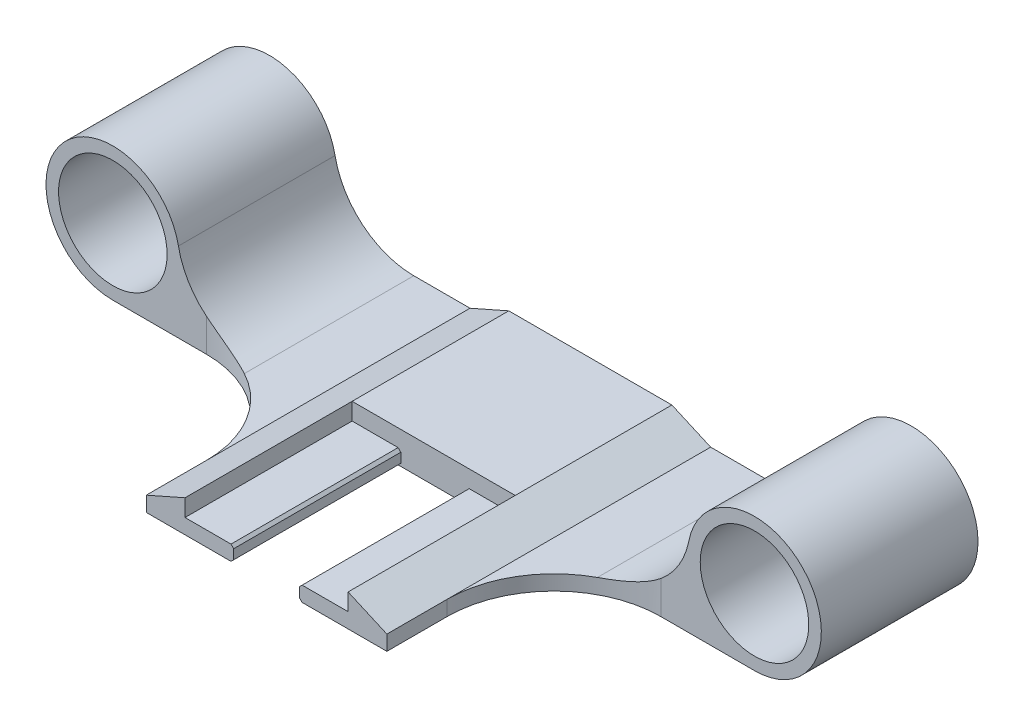
SolidWorks part; units mm, degrees
ref_plane "Front Plane" through (0, 0, 0) normal (0, 0, 1) x (1, 0, 0)
ref_plane "Top Plane" through (0, 0, 0) normal (0, 1, 0) x (1, 0, 0)
ref_plane "Right Plane" through (0, 0, 0) normal (1, 0, 0) x (0, 0, -1)
sketch "Sketch1" plane through (0, 0, 0) normal (0, 0, 1) x (1, 0, 0)
  line L1 (-22.5, -1.4) -> (-6.15, -1.4)
  line L2 (-22.5, -1.4) -> (-22.5, 1.4)
  line L3 (-15.25, 1.4) -> (-6.15, 1.4)
  line L4 (22.5, -1.4) -> (22.5, 1.4)
  line L5 (-22.5, -1.4) -> (22.5, 1.4) construction
  line L6 (-22.5, 1.4) -> (22.5, -1.4) construction
  line L8 (-6.15, -1.4) -> (-6.15, 1.4)
  line L10 (6.15, -1.4) -> (6.15, 1.4)
  line L11 (-6.15, -1.4) -> (6.15, 1.4) construction
  line L12 (-6.15, 1.4) -> (6.15, -1.4) construction
  line L13 (15.25, 1.4) -> (15.25, 4.6)
  line L14 (15.25, 4.6) -> (22.5, 1.4)
  line L15 (6.15, -1.4) -> (22.5, -1.4)
  line L16 (-15.25, 1.4) -> (-15.25, 4.6)
  line L17 (-15.25, 4.6) -> (-22.5, 1.4)
  line L19 (6.15, 1.4) -> (15.25, 1.4)
  point P0 (0, 0)
  point P6 (0, 0)
  point P11 (0, 0)
  point P14 (0, 1.4)
  point P16 (0, 0)
  point P17 (0, 0)
  dimension "D1" = 45
  dimension "D2" = 2.8
  dimension "D3" = 12.3
  dimension "D4" = 30.5
  dimension "D5" = 3.2
extrude "Boss-Extrude1" add sketch "Sketch1" along normal blind 31.25
sketch "Sketch3" plane through (0, 0, 0) normal (0, 0, 1) x (1, 0, 0)
  line L0 (22.5, 1.4) -> (15.25, 4.6)
  line L1 (15.25, 4.6) -> (-15.25, 4.6)
  line L5 (22.5, -1.4) -> (-22.5, -1.4)
  line L6 (-22.5, -1.4) -> (-22.5, 1.4)
  line L9 (22.5, 1.4) -> (22.5, -1.4)
  line L10 (-15.25, 4.6) -> (-22.5, 1.4)
  point P1 (0, 0)
extrude "Boss-Extrude3" add sketch "Sketch3" against normal blind 29.3
sketch "Sketch4" plane through (0, 0, 0) normal (0, 0, 1) x (1, 0, 0)
  line L0 (-60, -1.4) -> (-22.5, -1.4)
  line L1 (-33.0156, 1.4) -> (-22.5, 1.4)
  line L2 (-22.5, 1.4) -> (-22.5, -1.4)
  arc A0 (-47.7343, 13.5091) -> (-60, -1.4) centre (-60, 11.1) ccw
  circle A1 centre (-60, 11.1) radius 10.15
  arc A2 (-47.7343, 13.5091) -> (-33.0156, 1.4) centre (-33.0156, 16.4) ccw
  dimension "D3" = 25
  dimension "D4" = 20.3
  dimension "D2" = 15
  dimension "D1" = 60
extrude "Boss-Extrude4" add sketch "Sketch4" against normal up to surface (29.3 mm away) contours A2 A0 A1 region at (-69.2214, 18.6864, 0) up to face at (0, 1.5333, -29.3)
mirror "Mirror2" about plane through (0, 0, 0) normal (1, 0, 0) of "Boss-Extrude4"
fillet "Fillet1" radius 20 2 edges at (-22.5, 0, 0) (22.5, 0, 0)
chamfer "Chamfer1" distance 0.5 angle 45 4 edges at (6.15, -1.4, 15.625) (-6.15, -1.4, 15.625) (6.15, 1.4, 15.625) (-6.15, 1.4, 15.625)
